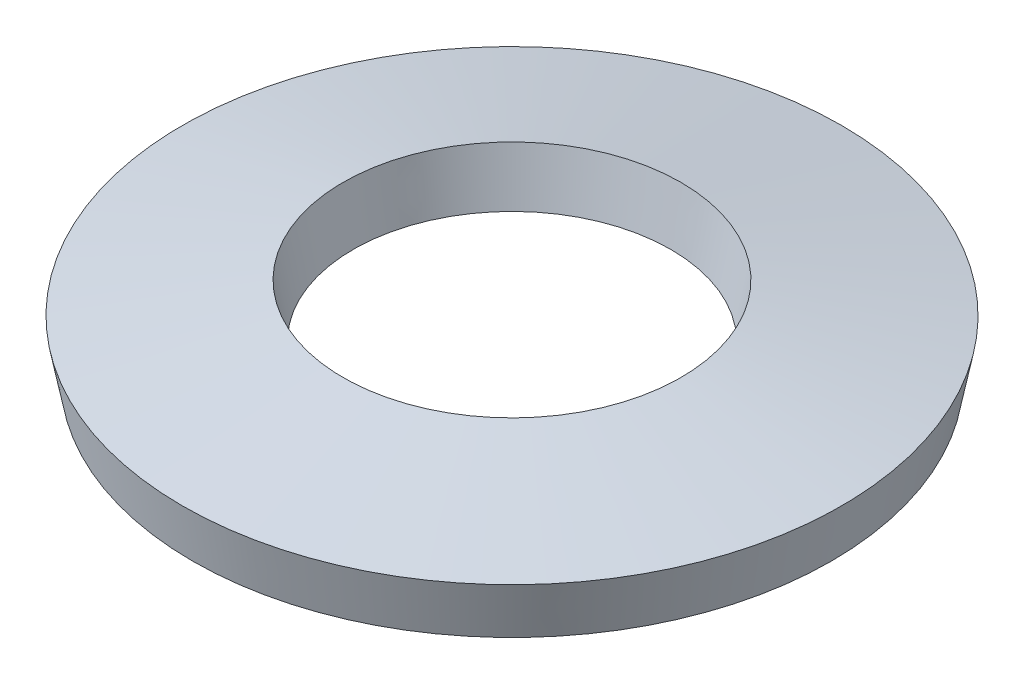
SolidWorks part; units mm, degrees
ref_plane "Front" through (0, 0, 0) normal (0, 0, 1) x (1, 0, 0)
ref_plane "Top" through (0, 0, 0) normal (0, 1, 0) x (1, 0, 0)
ref_plane "Right" through (0, 0, 0) normal (1, 0, 0) x (0, 0, -1)
sketch "Sketch1" plane through (0, 0, 0) normal (0, 0, 1) x (1, 0, 0)
  line L0 (5.3297, 0) -> (2.65, 0.5163)
  line L1 (2.65, 0.5163) -> (2.8203, 1.4)
  line L2 (2.8203, 1.4) -> (5.5, 0.8837)
  line L3 (5.5, 0.8837) -> (5.3297, 0)
  line L4 (0, 0) -> (0, 1.4) construction
  line L5 (-5.5, 0.8837) -> (-5.3297, 0) construction
  line L6 (-2.8203, 1.4) -> (-5.5, 0.8837) construction
  line L7 (-2.65, 0.5163) -> (-2.8203, 1.4) construction
  line L8 (-5.3297, 0) -> (-2.65, 0.5163) construction
  point P5 (2.7351, 0.9581)
  point P8 (-2.7351, 0.9581)
  dimension "D1" = 2.729
  dimension "ID" = 5.3
  dimension "OD" = 11
  dimension "Thickness" = 0.9
  dimension "Height" = 1.4
revolve "Revolve1" add sketch "Sketch1" angle 360 about L4
sketch "Sketch15" plane through (0, 0, 0) normal (0, 1, 0) x (1, 0, 0)
  circle A0 centre (0, 0) radius 5.5
  circle A1 centre (0, 0) radius 2.65
ref_plane "Contact Plane 1" through (0, 0, 0) normal (0, 1, 0) x (-1, 0, 0)
ref_plane "Contact Plane 2" through (0, 1.4, 0) normal (0, 1, 0) x (-1, 0, 0)
ref_axis "Center Axis 1" through (0, 0, 0) along (0, 1, 0)
